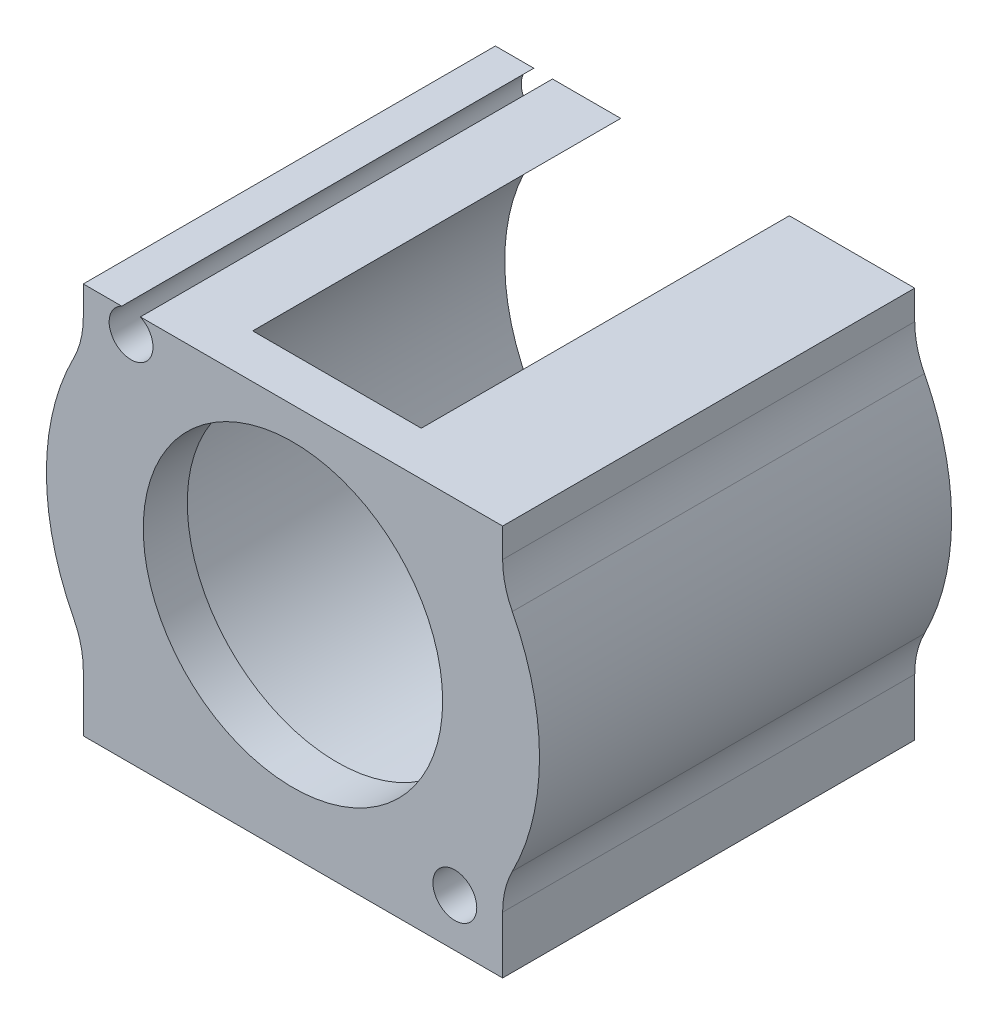
SolidWorks part; units mm, degrees
ref_plane "Front Plane" through (0, 0, 0) normal (0, 0, 1) x (1, 0, 0)
ref_plane "Top Plane" through (0, 0, 0) normal (0, 1, 0) x (1, 0, 0)
ref_plane "Right Plane" through (0, 0, 0) normal (1, 0, 0) x (0, 0, -1)
sketch "Sketch1" plane through (0, 0, 0) normal (0, 0, 1) x (1, 0, 0)
  line L1 (23.8125, -23.8125) -> (-23.8125, -23.8125)
  line L2 (23.8125, -23.8125) -> (23.8125, 23.8125)
  line L3 (23.8125, 23.8125) -> (-23.8125, 23.8125)
  line L4 (-23.8125, -23.8125) -> (-23.8125, 23.8125)
  line L5 (23.8125, -23.8125) -> (-23.8125, 23.8125) construction
  line L6 (23.8125, 23.8125) -> (-23.8125, -23.8125) construction
  circle A0 centre (0, 0) radius 21.25 construction
  circle A1 centre (0, 0) radius 22.75
  circle A2 centre (0, 0) radius 26 construction
  circle A3 centre (-18.3848, 18.3848) radius 2.4892
  circle A4 centre (18.3848, -18.3848) radius 2.4892
  point P0 (0, 0)
  dimension "D2" = 42.5
  dimension "D4" = 52
  dimension "D5" = 4.9784
  dimension "D1" = 47.625
  dimension "D3" = 1.5
extrude "Boss-Extrude1" add sketch "Sketch1" along normal blind 46.8
sketch "Sketch2" plane through (0, 0, 46.8) normal (0, 0, 1) x (1, 0, 0)
  line L0 (23.8125, -23.8125) -> (23.8125, 23.8125) construction
  line L1 (-23.8125, 23.8125) -> (23.8125, 23.8125)
  line L2 (-23.8125, 23.8125) -> (-23.8125, 20.6375)
  line L3 (-23.8125, 20.6375) -> (23.8125, 20.6375)
  line L4 (23.8125, 23.8125) -> (23.8125, 20.6375)
  line L5 (-23.8125, -23.8125) -> (23.8125, -23.8125) construction
  dimension "D1" = 44.45
extrude "Cut-Extrude1" cut sketch "Sketch2" against normal through all both and the other way through all
sketch "Sketch3" plane through (0, 0, 46.8) normal (0, 0, 1) x (1, 0, 0)
  line L0 (23.8125, -23.8125) -> (23.8125, 20.6375) construction
  line L1 (-23.8125, 20.6375) -> (-23.8125, -23.8125) construction
  line L2 (23.8125, -14.7297) -> (23.8125, 14.7297)
  line L3 (-23.8125, 14.7297) -> (-23.8125, -14.7297)
  arc A1 (-23.8125, 14.7297) -> (-23.8125, -14.7297) centre (0, 0) ccw
  arc A2 (23.8125, -14.7297) -> (23.8125, 14.7297) centre (0, 0) ccw
  dimension "D1" = 28
extrude "Boss-Extrude2" add sketch "Sketch3" against normal up to surface (46.8 mm away) up to face at (-4.5962, 3.5088, 0)
fillet "Fillet1" radius 10 4 edges at (23.8125, 14.7297, 23.4) (23.8125, -14.7297, 23.4) (-23.8125, -14.7297, 23.4) (-23.8125, 14.7297, 23.4)
sketch "Sketch4" plane through (0, 0, 46.8) normal (0, 0, 1) x (1, 0, 0)
  line L0 (-9.5737, 20.6375) -> (9.5737, 20.6375)
  circle A0 centre (0, 0) radius 17
  arc A1 (-9.5737, 20.6375) -> (9.5737, 20.6375) centre (0, 0) ccw construction
  arc A2 (-9.5737, 20.6375) -> (9.5737, 20.6375) centre (0, 0) ccw
  dimension "D1" = 34
extrude "Boss-Extrude3" add sketch "Sketch4" against normal blind 5
